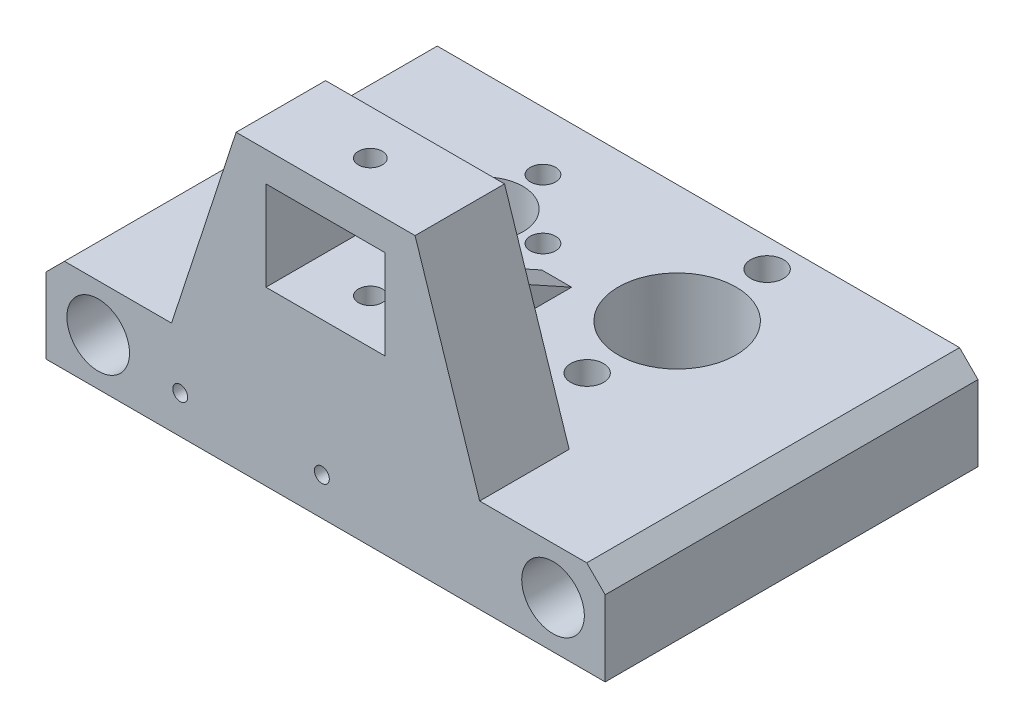
SolidWorks part; units mm, degrees
ref_plane "Front Plane" through (0, 0, 0) normal (0, 0, 1) x (1, 0, 0)
ref_plane "Top Plane" through (0, 0, 0) normal (0, 1, 0) x (1, 0, 0)
ref_plane "Right Plane" through (0, 0, 0) normal (1, 0, 0) x (0, 0, -1)
sketch "Sketch1" plane through (0, 0, 0) normal (0, 1, 0) x (1, 0, 0)
  line L0 (0, 34.15) -> (75, 34.15) construction
  line L1 (0, 0) -> (75, 0)
  line L2 (0, 0) -> (0, 50)
  line L3 (0, 50) -> (75, 50)
  line L4 (75, 0) -> (75, 50)
  line L5 (37.5, 50) -> (37.5, 0) construction
  line L6 (37.5, 34.15) -> (24.5, 34.15) construction
  line L7 (37.5, 34.15) -> (50.5, 34.15) construction
  circle A0 centre (24.5, 34.15) radius 5.3
  circle A1 centre (50.5, 34.15) radius 7.9
  point P15 (37.5, 34.15)
  dimension "D2" = 10.6
  dimension "D6" = 15.8
  dimension "D1" = 26
  dimension "D3" = 75
  dimension "D4" = 50
  dimension "D5" = 15.85
extrude "Boss-Extrude1" add sketch "Sketch1" along normal blind 0.1
sketch "Sketch2" plane through (0, 0.1, 0) normal (0, 1, 0) x (1, 0, 0)
  line L4 (0, 50) -> (12.5, 50)
  line L5 (0, 50) -> (0, 10)
  line L6 (0, 10) -> (12.5, 10)
  line L7 (12.5, 50) -> (12.5, 10)
  line L8 (75, 50) -> (62.5, 50)
  line L9 (75, 50) -> (75, 10)
  line L10 (75, 10) -> (62.5, 10)
  line L11 (62.5, 50) -> (62.5, 10)
  dimension "D1" = 40
  dimension "D3" = 12.5
extrude "Boss-Extrude2" add sketch "Sketch2" along normal blind 12.5
sketch "Sketch4" plane through (0, 0.1, 0) normal (0, 1, 0) x (1, 0, 0)
  line L0 (37.5, 0) -> (37.5, 50) construction
  line L1 (0, 0) -> (75, 0) construction
  line L2 (62.5, 50) -> (12.5, 50) construction
  line L4 (45.5, 0) -> (49.5, 0)
  line L5 (45.5, 0) -> (45.5, 12)
  line L6 (45.5, 12) -> (49.5, 12)
  line L7 (49.5, 0) -> (49.5, 12)
  line L8 (25.5, 0) -> (29.5, 0)
  line L9 (25.5, 0) -> (25.5, 12)
  line L10 (25.5, 12) -> (29.5, 12)
  line L11 (29.5, 0) -> (29.5, 12)
  dimension "D1" = 4
  dimension "D3" = 8
  dimension "D4" = 8
  dimension "D5" = 12
extrude "Boss-Extrude3" add sketch "Sketch4" along normal blind 35
sketch "Sketch5" plane through (0, 0, -12) normal (0, 0, -1) x (-1, 0, 0)
  line L0 (-49.5, 0.1) -> (-45.5, 0.1) construction
  line L1 (-49.5, 35.1) -> (-25.5, 35.1)
  line L2 (-49.5, 35.1) -> (-49.5, 39.1)
  line L3 (-49.5, 39.1) -> (-25.5, 39.1)
  line L4 (-25.5, 35.1) -> (-25.5, 39.1)
extrude "Boss-Extrude4" add sketch "Sketch5" against normal up to surface (12 mm away) up to face at (37.5, 11.75, 0)
sketch "Sketch7" plane through (0, 0.1, 0) normal (0, 1, 0) x (1, 0, 0)
  line L0 (50.5, 26.25) -> (50.5, 42.05) construction
  line L1 (24.5, 39.45) -> (24.5, 28.85) construction
  line L2 (29.8, 34.15) -> (19.2, 34.15) construction
  circle A1 centre (50.5, 22.08) radius 2.2
  circle A2 centre (50.5, 46.215) radius 2.2
  circle A3 centre (50.5, 34.15) radius 7.9 construction
  circle A4 centre (24.5, 34.15) radius 5.3 construction
  circle A6 centre (24.5, 42.15) radius 1.7
  circle A7 centre (16.5, 34.15) radius 1.7
  circle A8 centre (32.5, 34.15) radius 1.7
  circle A9 centre (24.5, 26.15) radius 1.7
  point P10 (50.5, 34.15)
  point P20 (24.5, 34.15)
  dimension "D3" = 4.4
  dimension "D6" = 3.4
  dimension "D1" = 12.065
  dimension "D2" = 12.07
  dimension "D4" = 8
  dimension "D5" = 8
extrude "Cut-Extrude4" cut sketch "Sketch7" against normal through all
sketch "Sketch8" plane through (0, 0.1, 0) normal (0, 1, 0) x (1, 0, 0)
  line L1 (45.5, 0) -> (29.5, 0)
  line L2 (45.5, 0) -> (45.5, 12)
  line L3 (45.5, 12) -> (29.5, 12)
  line L4 (29.5, 0) -> (29.5, 12)
extrude "Boss-Extrude5" add sketch "Sketch8" along normal blind 23
sketch "Sketch9" plane through (0, 0, 0) normal (0, 0, 1) x (1, 0, 0)
  line L0 (49.5, 39.1) -> (62.25, 0.1)
  line L1 (49.5, 0.1) -> (75, 0.1) construction
  line L2 (62.25, 0.1) -> (49.5, 0.1)
  line L3 (49.5, 0.1) -> (49.5, 39.1)
  line L4 (37.5, 23.1) -> (37.5, 35.1) construction
  line L5 (29.5, 23.1) -> (45.5, 23.1) construction
  line L6 (29.5, 35.1) -> (45.5, 35.1) construction
  line L7 (12.75, 0.1) -> (25.5, 0.1)
  line L8 (25.5, 39.1) -> (12.75, 0.1)
  line L9 (25.5, 0.1) -> (25.5, 39.1)
extrude "Boss-Extrude6" add sketch "Sketch9" against normal up to surface (12 mm away) up to face at (37.5, 19.6, -12)
sketch "Sketch6" plane through (0, 39.1, 0) normal (0, 1, 0) x (1, 0, 0)
  line L0 (49.5, 6) -> (25.5, 6) construction
  line L3 (37.5, 0) -> (37.5, 12) construction
  line L4 (49.5, 0) -> (25.5, 0) construction
  line L5 (25.5, 12) -> (49.5, 12) construction
  line L6 (25.5, 0) -> (25.5, 12) construction
  line L7 (49.5, 0) -> (49.5, 12) construction
  circle A0 centre (37.5, 6) radius 1.6
  dimension "D1" = 3.2
extrude "Cut-Extrude2" cut sketch "Sketch6" against normal blind 25
sketch "Sketch10" plane through (0, 0.1, 0) normal (0, 1, 0) x (1, 0, 0)
  line L0 (62.25, 12) -> (12.75, 12) construction
  line L1 (39.5, 12) -> (35.5, 12)
  line L2 (39.5, 12) -> (39.5, 50)
  line L3 (39.5, 50) -> (35.5, 50)
  line L4 (35.5, 12) -> (35.5, 50)
  line L5 (37.5, 12) -> (37.5, 50) construction
  line L6 (62.5, 50) -> (12.5, 50) construction
  point P6 (37.5, 50)
  dimension "D1" = 4
extrude "Boss-Extrude7" add sketch "Sketch10" along normal blind 2
sketch "Sketch11" plane through (39.5, 0, 0) normal (1, 0, 0) x (0, 0, -1)
  line L0 (50, 2.1) -> (12, 2.1)
  line L1 (12, 2.1) -> (12, 23.1)
  line L2 (12, 23.1) -> (50, 2.1)
extrude "Boss-Extrude8" add sketch "Sketch11" against normal up to surface (4 mm away) up to face at (35.5, 1.1, -31)
sketch "Sketch12" plane through (0, 0.1, 0) normal (0, 1, 0) x (1, 0, 0)
  line L1 (39.5, 12) -> (44.5, 12)
  line L2 (39.5, 12) -> (39.5, 16.6)
  line L3 (39.5, 16.6) -> (44.5, 16.6)
  line L4 (44.5, 12) -> (44.5, 16.6)
  line L5 (35.5, 12) -> (30.5, 12)
  line L6 (35.5, 12) -> (35.5, 16.6)
  line L7 (35.5, 16.6) -> (30.5, 16.6)
  line L8 (30.5, 12) -> (30.5, 16.6)
  dimension "D1" = 5
  dimension "D2" = 4.6
revolve "Revolve1" add sketch "Sketch12" angle 90 about L1 region at (33, 0.1, -14.3)
sketch "Sketch14" plane through (0, 0.1, 0) normal (0, 1, 0) x (1, 0, 0)
  line L1 (75, 0) -> (0, 0)
  line L2 (75, 0) -> (75, 10)
  line L3 (75, 10) -> (0, 10)
  line L4 (0, 0) -> (0, 10)
  line L5 (62.5, 10) -> (12.5, 10)
  line L6 (62.5, 10) -> (62.5, 50)
  line L7 (62.5, 50) -> (12.5, 50)
  line L8 (12.5, 10) -> (12.5, 50)
  circle A0 centre (50.5, 22.08) radius 2.2
  circle A1 centre (50.5, 22.08) radius 2.2 construction
  circle A2 centre (50.5, 34.15) radius 7.9
  circle A3 centre (50.5, 46.215) radius 2.2
  circle A4 centre (32.5, 34.15) radius 1.7
  circle A5 centre (24.5, 34.15) radius 5.3
  circle A6 centre (16.5, 34.15) radius 1.7
  circle A7 centre (24.5, 26.15) radius 1.7
  circle A8 centre (24.5, 42.15) radius 1.7
  circle A9 centre (24.5, 42.15) radius 1.7 construction
  circle A10 centre (24.5, 34.15) radius 5.3 construction
  circle A11 centre (50.5, 46.215) radius 2.2 construction
  circle A12 centre (50.5, 34.15) radius 7.9 construction
  circle M8 centre (50.5, 22.08) radius 2.2
  circle M9 centre (50.5, 46.215) radius 2.2
  circle M10 centre (50.5, 34.15) radius 7.9
  line M11 (39.5, 50) -> (39.5, 16.6)
  line M12 (39.5, 16.6) -> (44.5, 16.6)
  line M13 (44.5, 16.6) -> (44.5, 12)
  line M14 (44.5, 12) -> (62.25, 12)
  line M15 (62.25, 12) -> (62.25, 0)
  line M16 (62.25, 0) -> (75, 0)
  line M17 (75, 0) -> (75, 10)
  line M18 (75, 10) -> (62.5, 10)
  line M19 (62.5, 10) -> (62.5, 50)
  line M20 (62.5, 50) -> (39.5, 50)
extrude "Boss-Extrude9" add sketch "Sketch14" along normal up to surface (12.5 mm away) contours L3 M19 M20 M11 M12 M13 M14 M15 M9 M10 M8 | L3 M18 M15 M16 M17 | L8 L3 L7 A8 A7 A6 A5 A4 M15 M14 M13 M12 M11 | L4 L1 L3 M15 region at (68.625, 0.1, -5) region at (31.125, 0.1, -5) region at (62.2961, 0.1, -11) region at (27.6472, 0.1, -28.2982) up to face at (68.75, 12.6, -30)
sketch "Sketch3" plane through (0, 0, -50) normal (0, 0, -1) x (-1, 0, 0)
  line L0 (-37.5, 0) -> (-37.5, 50000) construction
  line L1 (-75, 0) -> (0, 0) construction
  line L3 (-72.5251, 12.6) -> (-75, 12.6)
  line L4 (-75, 12.6) -> (0, 12.6) construction
  line L5 (-75, 12.6) -> (-75, 10.1251)
  line L6 (-75, 12.6) -> (-75, 0) construction
  line L7 (-75, 10.1251) -> (-72.5251, 12.6)
  line L12 (-37.5, 12.6) -> (-37.5, 0) construction
  line L13 (-61, 6.3) -> (-75, 6.3) construction
  line L14 (-14, 6.3) -> (0, 6.3) construction
  line L15 (-37.5, 12.6) -> (-37.5, 0) construction
  line L19 (0, 10.1251) -> (-2.4749, 12.6)
  line L20 (0, 12.6) -> (0, 10.1251)
  line L21 (-2.4749, 12.6) -> (0, 12.6)
  line L22 (-75, 12.6) -> (-75, 0) construction
  circle A0 centre (-68, 6.3) radius 4.2
  circle A1 centre (-7, 6.3) radius 4.2
  point P4 (-37.5, 0)
  dimension "D1" = 8.4
  dimension "D2" = 3.5
  dimension "D3" = 14
extrude "Cut-Extrude1" cut sketch "Sketch3" against normal through all
sketch "Sketch15" plane through (0, 0, 0) normal (0, 0, 1) x (1, 0, 0)
  line L0 (0, 5.0626) -> (75, 5.0626) construction
  line L1 (0, 10.1251) -> (0, 0) construction
  line L2 (75, 10.1251) -> (75, 0) construction
  line L3 (37.5, 39.1) -> (37.5, 0) construction
  line L4 (49.5, 39.1) -> (25.5, 39.1) construction
  line L5 (0, 0) -> (75, 0) construction
  circle A0 centre (18, 5.0626) radius 1
  circle A1 centre (37, 5.0626) radius 1
  dimension "D3" = 2
  dimension "D1" = 19
  dimension "D2" = 0.5
extrude "Cut-Extrude5" cut sketch "Sketch15" against normal blind 8
equation "\"8mm hole\" = 8.4mm"
equation "\"22mm hole\"= 23mm"
equation "\"15mm hole\"= 15.8mm"
equation "\"D6@Sketch1\"= \"15mm hole\""
equation "\"D1@Sketch3\"= \"8mm hole\""
equation "\"bed height offset\"= 3mm"
